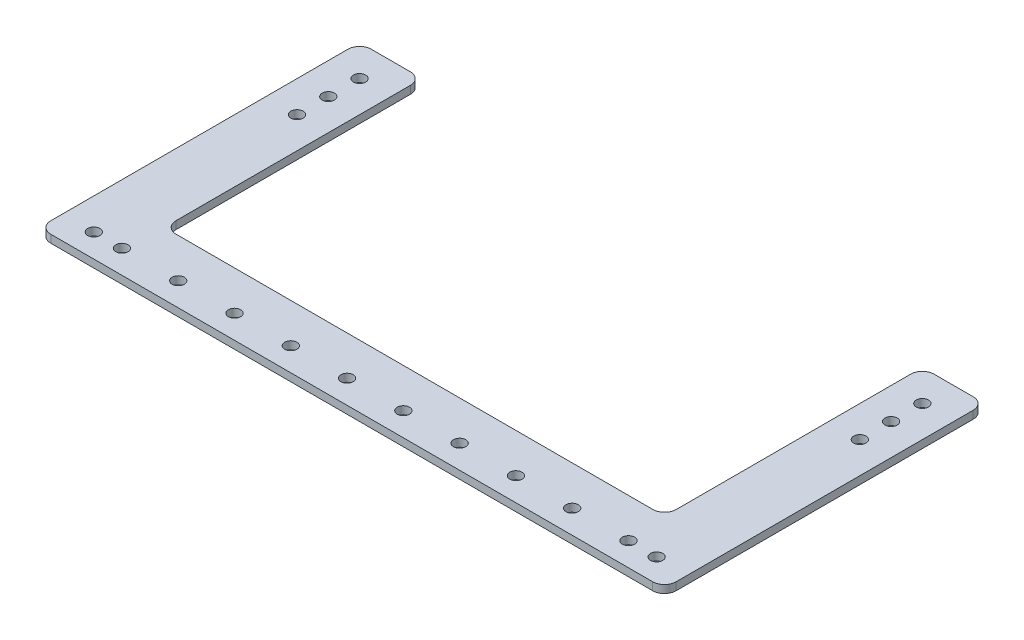
SolidWorks part; units mm, degrees
material "6061-T6 (SS)"
ref_plane "Front Plane" through (0, 0, 0) normal (0, 0, 1) x (1, 0, 0)
ref_plane "Top Plane" through (0, 0, 0) normal (0, 1, 0) x (1, 0, 0)
ref_plane "Right Plane" through (0, 0, 0) normal (1, 0, 0) x (0, 0, -1)
sketch "Sketch2" plane through (0, 0, 0) normal (0, 1, 0) x (1, 0, 0)
  line L0 (0, 65.0875) -> (0, -65.0875) construction
  line L1 (-127, -65.0875) -> (127, -65.0875)
  line L2 (-127, -65.0875) -> (-127, 65.0875)
  line L3 (-127, 65.0875) -> (127, 65.0875)
  line L4 (127, -65.0875) -> (127, 65.0875)
  line L5 (-127, -65.0875) -> (127, 65.0875) construction
  line L6 (-127, 65.0875) -> (127, -65.0875) construction
  line L7 (-101.6, 65.0875) -> (101.6, 65.0875)
  line L8 (-101.6, 65.0875) -> (-101.6, -39.624)
  line L9 (-101.6, -39.624) -> (101.6, -39.624)
  line L10 (101.6, 65.0875) -> (101.6, -39.624)
  line L11 (127, 65.0875) -> (101.6, 65.0875) construction
  line L12 (127, 65.0875) -> (127, -39.624) construction
  line L13 (127, -39.624) -> (101.6, -39.624) construction
  line L14 (101.6, 65.0875) -> (101.6, -39.624) construction
  circle A0 centre (-114.3, 52.3875) radius 2.4892
  circle A1 centre (-114.3, 39.6875) radius 2.4892
  circle A2 centre (-114.3, 26.9875) radius 2.4892
  circle A6 centre (114.3, 26.9875) radius 2.4892
  circle A7 centre (114.3, 39.6875) radius 2.4892
  circle A8 centre (114.3, 52.3875) radius 2.4892
  point P0 (0, 0)
  point P10 (0, -39.624)
  point P11 (0, -65.0875)
  dimension "D8" = 4.9784
  dimension "D1" = 254
  dimension "D2" = 130.175
  dimension "D3" = 203.2
  dimension "D4" = 25.4635
  dimension "D5" = 12.7
  dimension "D6" = 12.7
  dimension "D7" = 12.7
  dimension "D9" = 12.7
  dimension "D10" = 12.7
  dimension "D11" = 12.7
extrude "Boss-Extrude1" add sketch "Sketch2" along normal blind 3.175 contours L3 L10 L9 L8 L2 L1 L4 A7 A0 A1 A2 A6 A8 region at (-124.1459, 0, 0)
fillet "Fillet1" radius 4.7625 8 edges at (127, 1.5875, -65.0875) (-127, 1.5875, 65.0875) (-127, 1.5875, -65.0875) (-101.6, 1.5875, -65.0875) (-101.6, 1.5875, 39.624) (101.6, 1.5875, 39.624) (101.6, 1.5875, -65.0875) (127, 1.5875, 65.0875)
sketch "Sketch3" plane through (0, 3.175, 0) normal (0, 1, 0) x (1, 0, 0)
  line L0 (-127, -60.325) -> (-127, 60.325) construction
  line L1 (-122.2375, -65.0875) -> (122.2375, -65.0875) construction
  line L2 (102.87, -55.5625) -> (114.3, -55.5625) construction
  line L3 (-96.8375, -39.624) -> (96.8375, -39.624) construction
  line L4 (-38.1, -39.624) -> (-38.1, -65.0875) construction
  line L5 (-114.3, -55.5625) -> (-102.87, -55.5625) construction
  line L7 (-101.6, -39.624) -> (101.6, -39.624) construction
  line L8 (-42.0688, -39.624) -> (-34.1313, -39.624) construction
  line L9 (-42.0688, -39.624) -> (-42.0688, -65.0875) construction
  line L10 (-42.0688, -65.0875) -> (-34.1313, -65.0875) construction
  line L11 (-34.1313, -39.624) -> (-34.1313, -65.0875) construction
  line L12 (-127, -65.0875) -> (127, -65.0875) construction
  circle A38 centre (-102.87, -55.5625) radius 2.4892
  circle A40 centre (-80.01, -55.5625) radius 2.4892
  circle A41 centre (-114.3, -55.5625) radius 2.4892
  circle A55 centre (-57.15, -55.5625) radius 2.4892
  circle A63 centre (114.3, -55.5625) radius 2.4892
  circle A64 centre (-114.3, 26.9875) radius 2.4892 construction
  circle A65 centre (-34.29, -55.5625) radius 2.4892
  circle A66 centre (-11.43, -55.5625) radius 2.4892
  circle A67 centre (11.43, -55.5625) radius 2.4892
  circle A68 centre (34.29, -55.5625) radius 2.4892
  circle A69 centre (57.15, -55.5625) radius 2.4892
  circle A74 centre (80.01, -55.5625) radius 2.4892
  circle A75 centre (102.87, -55.5625) radius 2.4892
  point P48 (-38.1, -39.624)
  dimension "D1" = 22.86
  dimension "D6" = 88.9
  dimension "D2" = 12.7
  dimension "D3" = 9.525
  dimension "D4" = 10
  dimension "D7" = 7.9375
extrude "Cut-Extrude1" cut sketch "Sketch3" against normal through all
